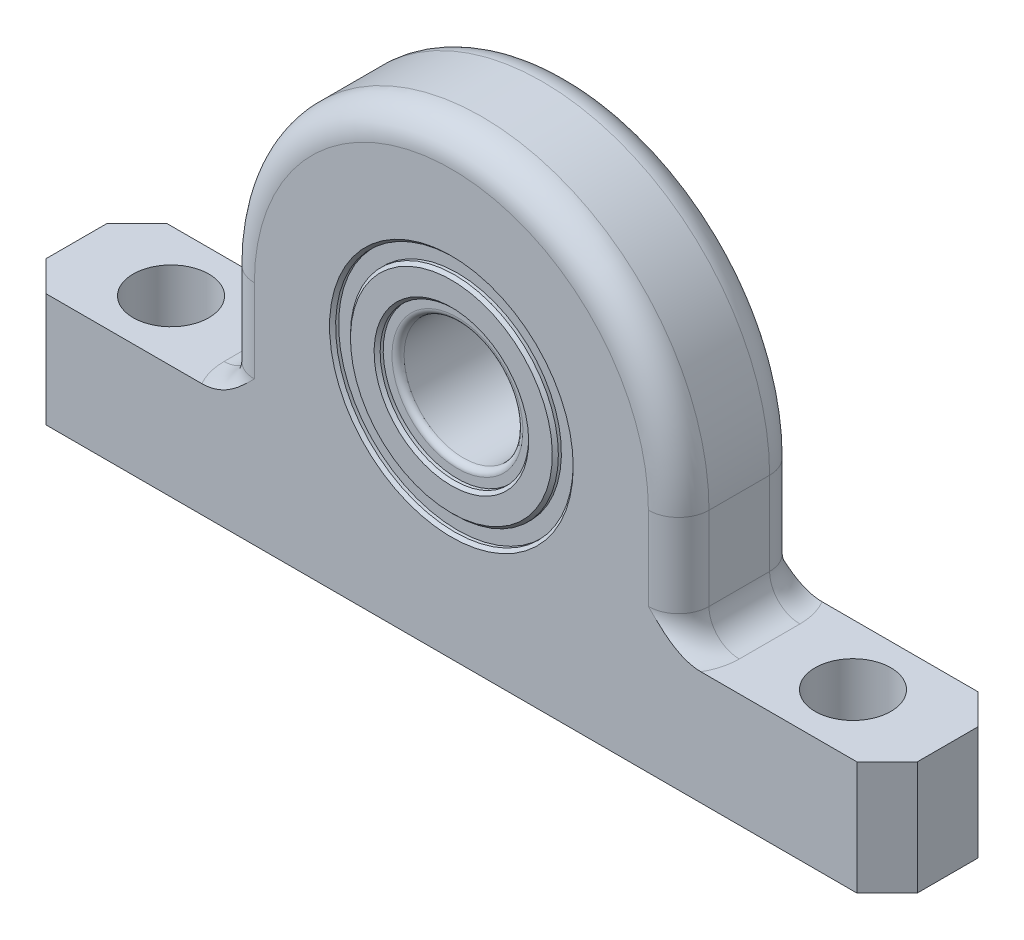
SolidWorks part; units mm, degrees
ref_plane "Front Plane" through (0, 0, 0) normal (0, 0, 1) x (1, 0, 0)
ref_plane "Top Plane" through (0, 0, 0) normal (0, 1, 0) x (1, 0, 0)
ref_plane "Right Plane" through (0, 0, 0) normal (1, 0, 0) x (0, 0, -1)
sketch "Sketch1" plane through (0, 0, 0) normal (0, 0, 1) x (1, 0, 0)
  line L0 (9.525, 0) -> (9.525, -4.7625)
  line L1 (9.525, -4.7625) -> (18.2562, -4.7625)
  line L2 (18.2562, -4.7625) -> (18.2562, -9.525)
  line L3 (18.2562, -9.525) -> (-18.2562, -9.525)
  line L4 (-18.2562, -9.525) -> (-18.2563, -4.7625)
  line L5 (-18.2563, -4.7625) -> (-9.525, -4.7625)
  line L6 (-9.525, -4.7625) -> (-9.525, 0)
  circle A0 centre (0, 0) radius 2.4892
  arc A1 (9.525, 0) -> (-9.525, 0) centre (0, 0) ccw
  circle A2 centre (0, 0) radius 4.9784
  dimension "D1" = 9.9568
  dimension "shaft dia" = 4.9784
  dimension "I" = 19.05
  dimension "G" = 4.7625
  dimension "B" = 36.5125
  dimension "A" = 9.525
sketch "Sketch2" plane through (0, 0, 0) normal (0, 1, 0) x (1, 0, 0)
  line L0 (0, 2.54) -> (0, -2.54) construction
  line L1 (-14.2875, 0) -> (14.2875, 0) construction
  circle A0 centre (14.2875, 0) radius 1.5875
  circle A1 centre (-14.2875, 0) radius 1.5875
  dimension "F" = 3.175
  dimension "E" = 5.08
  dimension "C" = 28.575
sketch "Sketch3" plane through (0, 0, 0) normal (0, 0, 1) x (1, 0, 0)
  line L0 (9.525, 0) -> (9.525, -4.7625) construction
  line L1 (18.2562, -4.7625) -> (18.2562, -9.525) construction
  line L2 (9.525, -4.7625) -> (18.2562, -4.7625) construction
  line L3 (18.2562, -9.525) -> (-18.2562, -9.525) construction
  line L4 (-18.2562, -9.525) -> (-18.2563, -4.7625) construction
  line L5 (-18.2563, -4.7625) -> (-9.525, -4.7625) construction
  line L6 (-9.525, -4.7625) -> (-9.525, 0) construction
  line L7 (9.525, 0) -> (9.525, -4.7625)
  line L8 (18.2562, -4.7625) -> (18.2562, -9.525)
  line L9 (9.525, -4.7625) -> (18.2562, -4.7625)
  line L10 (18.2562, -9.525) -> (-18.2562, -9.525)
  line L11 (-18.2562, -9.525) -> (-18.2563, -4.7625)
  line L12 (-18.2563, -4.7625) -> (-9.525, -4.7625)
  line L13 (-9.525, -4.7625) -> (-9.525, 0)
  arc A0 (9.525, 0) -> (-9.525, 0) centre (0, 0) ccw construction
  circle A1 centre (0, 0) radius 4.9784 construction
  arc A2 (9.525, 0) -> (-9.525, 0) centre (0, 0) ccw
  circle A3 centre (0, 0) radius 4.9784
extrude "Extrude1" add sketch "Sketch3" along normal up to vertex (2.54 mm away) and the other way up to vertex (2.54 mm away) up to point (0, 0, 2.54) other way up to point (0, 0, -2.54)
sketch "Sketch4" plane through (0, -4.7625, 0) normal (0, 1, 0) x (1, 0, 0)
  line L0 (-18.2563, 2.54) -> (-18.2562, 1.27)
  line L1 (-18.2563, -2.54) -> (-18.2563, 2.54) construction
  line L2 (-18.2562, 1.27) -> (-16.9863, 2.54)
  line L3 (-9.525, 2.54) -> (-18.2563, 2.54) construction
  line L4 (-16.9863, 2.54) -> (-18.2563, 2.54)
  line L5 (0, 0) -> (0, 2.54) construction
  line L6 (0, 0) -> (-14.2875, 0) construction
  line L7 (16.9863, 2.54) -> (18.2563, 2.54)
  line L8 (18.2562, 1.27) -> (16.9863, 2.54)
  line L9 (18.2563, 2.54) -> (18.2562, 1.27)
  line L10 (18.2563, -2.54) -> (18.2562, -1.27)
  line L11 (18.2562, -1.27) -> (16.9863, -2.54)
  line L12 (16.9863, -2.54) -> (18.2563, -2.54)
  line L13 (-16.9863, -2.54) -> (-18.2563, -2.54)
  line L14 (-18.2562, -1.27) -> (-16.9863, -2.54)
  line L15 (-18.2563, -2.54) -> (-18.2562, -1.27)
  circle A0 centre (-14.2875, 0) radius 1.5875 construction
  circle A1 centre (14.2875, 0) radius 1.5875 construction
  circle A2 centre (-14.2875, 0) radius 1.5875
  circle A3 centre (14.2875, 0) radius 1.5875
  dimension "D1" = 45
  dimension "D2" = 1.27
extrude "Cut-Extrude1" cut sketch "Sketch4" against normal through all
fillet "Fillet1" radius 1.27 6 edges at (9.525, -2.3812, -2.54) (-9.525, -2.3812, -2.54) (9.525, -2.3812, 2.54) (-9.525, -2.3812, 2.54) (0, 9.525, -2.54) (0, 9.525, 2.54)
fillet "Fillet2" radius 1.27 6 edges at (-9.153, -4.7625, 2.168) (-9.153, -4.7625, -2.168) (9.153, -4.7625, 2.168) (9.153, -4.7625, -2.168) (-9.525, -4.7625, 0) (9.525, -4.7625, 0)
chamfer "Chamfer1" distance 0.127 angle 45 2 edges at (4.9784, 0, -2.54) (4.9784, 0, 2.54)
sketch "Sketch5" plane through (0, 0, 0) normal (1, 0, 0) x (0, 0, -1)
  line L0 (0, 0) -> (0, 4.9784) construction
  line L1 (0, 4.9784) -> (0, -4.9784) construction
  line L2 (0, 2.4892) -> (0, -2.4892) construction
  line L3 (-2.286, 4.9784) -> (-2.286, 4.3561)
  line L4 (-2.286, 4.3561) -> (-2.54, 4.3561)
  line L5 (-2.54, 4.3561) -> (-2.54, 3.1115)
  line L6 (-2.54, 3.1115) -> (-2.286, 3.1115)
  line L7 (-2.286, 3.1115) -> (-2.286, 2.4892)
  line L8 (-2.286, 2.4892) -> (2.286, 2.4892)
  line L9 (0, 2.4892) -> (0, 4.9784) construction
  line L10 (-2.286, 4.9784) -> (2.286, 4.9784)
  line L11 (-2.54, 8.255) -> (-2.54, 0) construction
  line L12 (2.286, 3.1115) -> (2.286, 2.4892)
  line L13 (2.54, 3.1115) -> (2.286, 3.1115)
  line L14 (2.54, 4.3561) -> (2.54, 3.1115)
  line L15 (2.286, 4.3561) -> (2.54, 4.3561)
  line L16 (2.286, 4.9784) -> (2.286, 4.3561)
  line L17 (0, 0) -> (-2.54, 0) construction
  point P6 (0, 2.4892)
  dimension "D1" = 0.254
  dimension "D2" = 2.4892
  dimension "D3" = 1.2446
revolve "Revolve1" add sketch "Sketch5" angle 360 about L17
fillet "Fillet3" radius 0.254 2 edges at (0, 2.4892, 2.286) (0, 2.4892, -2.286)
chamfer "Chamfer2" distance 0.127 angle 45 4 edges at (0, 3.1115, -2.54) (0, 4.3561, -2.54) (0, 4.3561, 2.54) (0, 3.1115, 2.54)
equation "\"D1@Sketch1\" = \"shaft dia@Sketch1\"*2."
equation "\"D2@Sketch4\" = \"E@Sketch2\"/4"
equation "\"D1@Fillet1\" = \"D2@Sketch4\""
equation "\"D1@Fillet2\" = \"D1@Fillet1\""
equation "\"D3@Sketch5\" = \"D2@Sketch5\"/2"
